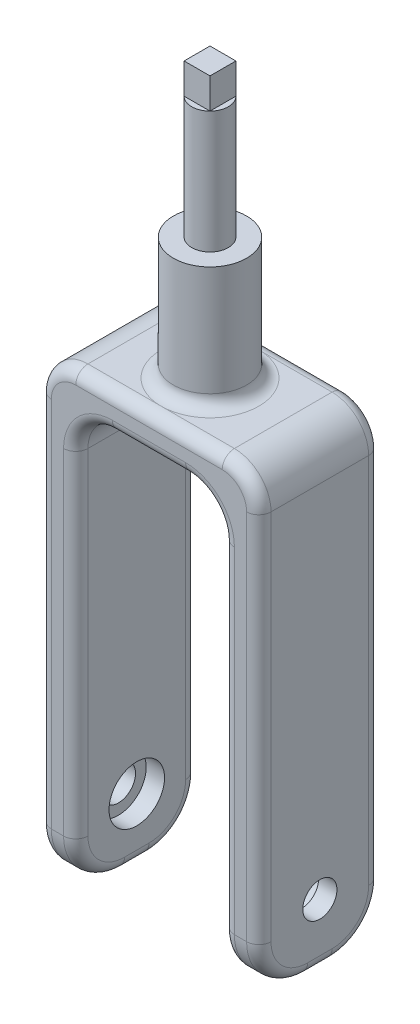
SolidWorks part; units mm, degrees
ref_plane "前视基准面" through (0, 0, 0) normal (0, 0, 1) x (1, 0, 0)
ref_plane "上视基准面" through (0, 0, 0) normal (0, 1, 0) x (1, 0, 0)
ref_plane "右视基准面" through (0, 0, 0) normal (1, 0, 0) x (0, 0, -1)
sketch "草图1" plane through (0, 0, 0) normal (0, 1, 0) x (1, 0, 0)
  line L1 (18, 10) -> (-18, 10)
  line L2 (18, 10) -> (18, -10)
  line L3 (18, -10) -> (-18, -10)
  line L4 (-18, 10) -> (-18, -10)
  line L5 (18, 10) -> (-18, -10) construction
  line L6 (18, -10) -> (-18, 10) construction
  point P0 (0, 0)
extrude "凸台-拉伸1" add sketch "草图1" against normal blind 75
sketch "草图2" plane through (0, 0, 0) normal (0, 1, 0) x (1, 0, 0)
  circle A0 centre (0, 0) radius 6
extrude "凸台-拉伸2" add sketch "草图2" along normal blind 20
sketch "草图7" plane through (0, 20, 0) normal (0, 1, 0) x (1, 0, 0)
  circle A0 centre (0, 0) radius 3
extrude "凸台-拉伸3" add sketch "草图7" along normal blind 25
sketch "草图8" plane through (0, 45, 0) normal (0, 1, 0) x (1, 0, 0)
  line L1 (2.1213, -2.1213) -> (-2.1213, -2.1213)
  line L2 (2.1213, -2.1213) -> (2.1213, 2.1213)
  line L3 (2.1213, 2.1213) -> (-2.1213, 2.1213)
  line L4 (-2.1213, -2.1213) -> (-2.1213, 2.1213)
  line L5 (2.1213, -2.1213) -> (-2.1213, 2.1213) construction
  line L6 (2.1213, 2.1213) -> (-2.1213, -2.1213) construction
  circle A0 centre (0, 0) radius 3 construction
  point P0 (0, 0)
extrude "切除-拉伸6" cut sketch "草图8" against normal blind 5 flip side to cut
sketch "草图3" plane through (0, 0, 10) normal (0, 0, 1) x (1, 0, 0)
  line L0 (-18, -75) -> (18, -75) construction
  line L1 (-12, -75) -> (12, -75)
  line L2 (-12, -75) -> (-12, -6)
  line L3 (-12, -6) -> (12, -6)
  line L4 (12, -75) -> (12, -6)
extrude "切除-拉伸1" cut sketch "草图3" against normal through all
fillet "圆角1" radius 6 4 edges at (-18, 0, 0) (18, 0, 0) (12, -6, 0) (-12, -6, 0)
fillet "圆角4" radius 2 1 edges at (0, 0, 6)
fillet "圆角3" radius 8 4 edges at (15, -75, -10) (15, -75, 10) (-15, -75, -10) (-15, -75, 10)
fillet "圆角2" radius 2 32 edges at (-18, -75, 0) (-18, -36.5, -10) (-16.2426, -1.7574, -10) (0, 0, -10) (16.2426, -1.7574, -10) (18, -36.5, -10) (18, -75, 0) (18, -36.5, 10) (16.2426, -1.7574, 10) (0, 0, 10) (-16.2426, -1.7574, 10) (-18, -36.5, 10) (-10.2426, -7.7574, 10) (0, -6, 10) (10.2426, -7.7574, 10) (12, -39.5, 10) (12, -75, 0) (12, -39.5, -10) (10.2426, -7.7574, -10) (0, -6, -10) (-10.2426, -7.7574, -10) (-12, -39.5, -10) (-12, -75, 0) (-12, -39.5, 10) (12, -72.6569, 7.6569) (12, -72.6569, -7.6569) (-12, -72.6569, -7.6569) (-12, -72.6569, 7.6569) (-18, -72.6569, 7.6569) (-18, -72.6569, -7.6569) (18, -72.6569, -7.6569) (18, -72.6569, 7.6569)
sketch "草图4" plane through (18, 0, 0) normal (1, 0, 0) x (0, 0, -1)
  circle A0 centre (0, -65) radius 2.8
extrude "切除-拉伸2" cut sketch "草图4" against normal through all
sketch "草图6" plane through (12, 0, 0) normal (1, 0, 0) x (0, 0, -1)
  circle A0 centre (0, -65) radius 4.55
extrude "切除-拉伸4" cut sketch "草图6" along normal blind 3
mirror "镜向1" about plane through (0, 0, 0) normal (1, 0, 0) of "切除-拉伸4"
